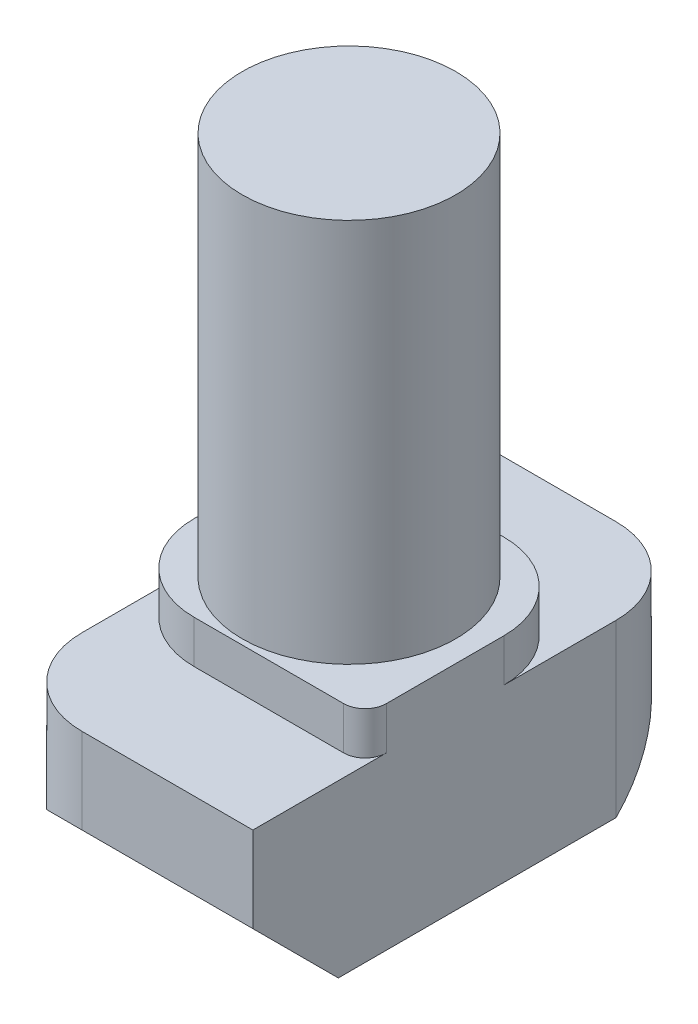
SolidWorks part; units mm, degrees
ref_plane "Front Plane" through (0, 0, 0) normal (0, 0, 1) x (1, 0, 0)
ref_plane "Top Plane" through (0, 0, 0) normal (0, 1, 0) x (1, 0, 0)
ref_plane "Right Plane" through (0, 0, 0) normal (1, 0, 0) x (0, 0, -1)
ref_axis "Axis_X" through (-88.99, 0, 0) along (1, 0, 0)
ref_axis "Axis_Y" through (0, 55, 0) along (0, -1, 0)
ref_axis "Axis_Z" through (0, 0, -88.99) along (0, 0, 1)
sketch "Sketch1" plane through (0, 0, 0) normal (1, 0, 0) x (0, 0, -1)
  line L0 (-2.625, 0) -> (2.625, 0)
  line L1 (2.625, 0) -> (2.625, -1)
  line L2 (2.625, -1) -> (5.25, -1)
  line L3 (5.25, -1) -> (5.25, -3)
  line L4 (5.25, -3) -> (3.25, -5)
  line L5 (3.25, -5) -> (-3.25, -5)
  line L6 (-3.25, -5) -> (-5.25, -3)
  line L7 (-5.25, -3) -> (-5.25, -1)
  line L8 (-5.25, -1) -> (-2.625, -1)
  line L9 (-2.625, -1) -> (-2.625, 0)
  line L10 (0, 0) -> (0, -5) construction
  dimension "FIX_1" = 45
  dimension "MSM_101" = 10.5
  dimension "KSS_101" = 5.25
  dimension "MSM_103" = 4
  dimension "MSM_104" = 2
  dimension "FIX_20" = 1
extrude "Boss-Extrude1" add sketch "Sketch1" along normal mid plane 6
fillet "Fillet1" radius 2 2 edges at (3, -2, -5.25) (-3, -2, 5.25)
fillet "Fillet2" radius 2 2 edges at (3, -0.5, -2.625) (-3, -0.5, 2.625)
fillet "Fillet3" radius 0.5 2 edges at (-3, -0.5, -2.625) (3, -0.5, 2.625)
sketch "Sketch2" plane through (0, 0, 0) normal (0, 0, 1) x (1, 0, 0)
  line L0 (0, 0) -> (2.5, 0)
  line L1 (2.5, 0) -> (-1, 0) construction
  line L2 (2.5, 0) -> (2.5, 9)
  line L3 (2.5, 9) -> (0, 9)
  line L4 (0, 9) -> (0, 0) construction
  line L5 (1, -1) -> (-2.5, -1) construction
  line L6 (0, 9) -> (0, 0)
  dimension "MSM_109" = 5
  dimension "MSM_108" = 10
revolve "Revolve1" add sketch "Sketch2" angle 360 about axis through (0, 55, 0) along (0, -1, 0)
cosmetic thread "Thread1" parameters "ATD_101"=4.134
equation "\"Factor\"= 1.082532"
equation "\"KSS_101@Sketch1\"= \"MSM_101@Sketch1\" / 2"
